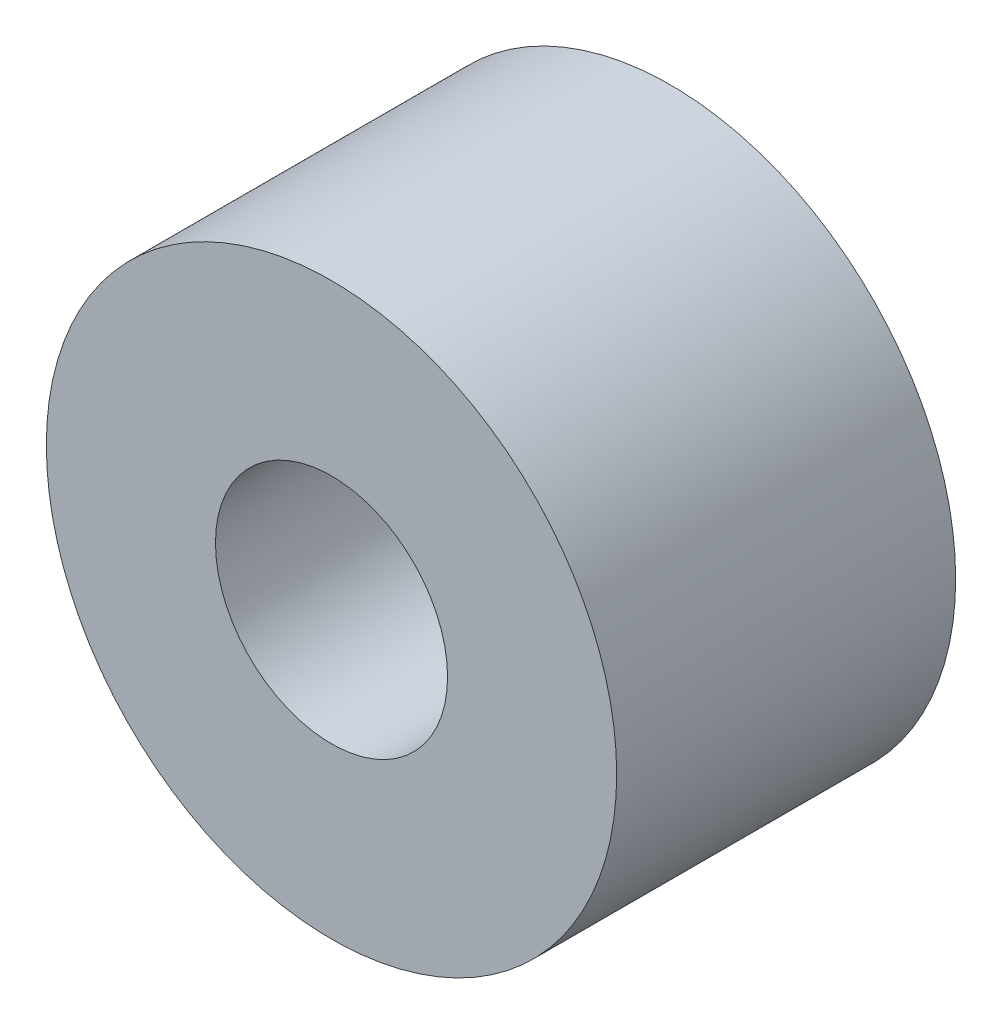
SolidWorks part; units mm, degrees
ref_plane "Front Plane" through (0, 0, 0) normal (0, 0, 1) x (1, 0, 0)
ref_plane "Top Plane" through (0, 0, 0) normal (0, 1, 0) x (1, 0, 0)
ref_plane "Right Plane" through (0, 0, 0) normal (1, 0, 0) x (0, 0, -1)
sketch "Sketch1" plane through (0, 0, 4.7625) normal (0, 0, 1) x (1, 0, 0)
  circle A1 centre (0, 0) radius 4.915
  circle A2 centre (0, 0) radius 2
  circle A3 centre (0, 0) radius 4.915 construction
  dimension "D1" = 4
extrude "Boss-Extrude1" add sketch "Sketch1" along normal blind 5.842 contours A1 A2 region at (-4.776, 0, 4.7625)
